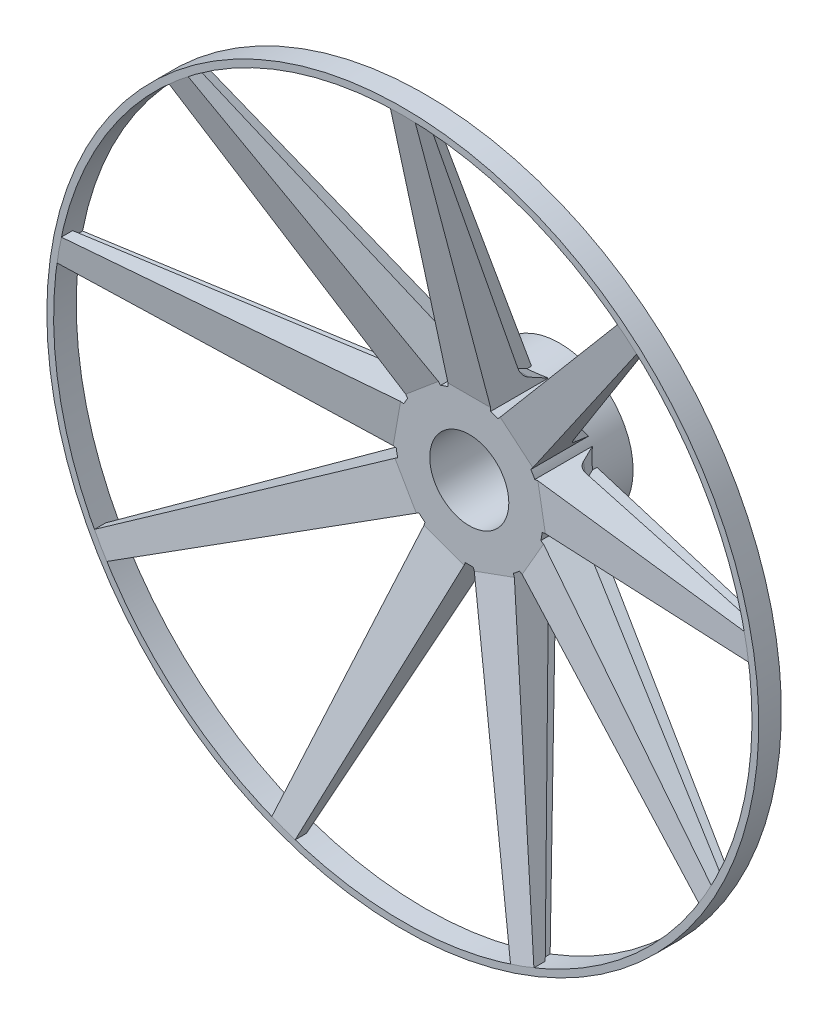
SolidWorks part; units mm, degrees
ref_plane "Front Plane" through (0, 0, 0) normal (0, 0, 1) x (1, 0, 0)
ref_plane "Top Plane" through (0, 0, 0) normal (0, 1, 0) x (1, 0, 0)
ref_plane "Right Plane" through (0, 0, 0) normal (1, 0, 0) x (0, 0, -1)
sketch "Sketch1" plane through (0, 0, 0) normal (0, 0, 1) x (1, 0, 0)
  line L0 (-20.031, 0) -> (20.031, 0) construction
  line L1 (0, 20.031) -> (0, -20.031) construction
  circle A1 centre (0, 0) radius 17.5
  circle A2 centre (0, 0) radius 32.5
  dimension "D1" = 35
  dimension "D2" = 65
extrude "Boss-Extrude1" add sketch "Sketch1" along normal blind 40
sketch "Sketch2" plane through (0, 0, 0) normal (0, 0, -1) x (-1, 0, 0)
  point P0 (0, 0)
sketch "Sketch3" plane through (0, 0, 0) normal (0, 1, 0) x (1, 0, 0)
  line L0 (0, 8.7146) -> (0, -51.2596) construction
sketch "Sketch4" plane through (0, 0, 0) normal (1, 0, 0) x (0, 0, -1)
  line L0 (-40, 32.5) -> (-15, 32.5)
  line L3 (-69.4044, 154.5) -> (-40, 32.5)
  line L4 (8.7146, 0) -> (-51.2596, 0) construction
  line L6 (-59.4044, 154.5) -> (-69.4044, 154.5)
  line L7 (-15, 32.5) -> (-59.4044, 154.5)
  dimension "D1" = 154.5
  dimension "D2" = 70
sketch "Sketch5" plane through (0, 0, 0) normal (0, 0, -1) x (-1, 0, 0)
extrude "Boss-Extrude2" add sketch "Sketch4" along normal blind 9.5 and the other way blind 9.5
sketch "Sketch6" plane through (0, 0, 40) normal (0, 0, 1) x (1, 0, 0)
  line L0 (-9.5, 32.5) -> (-9.5, 30.5512)
  line L1 (-9.5, 30.5512) -> (9.5, 30.5512)
  line L2 (9.5, 30.5512) -> (9.5, 32.5)
  line L3 (-9.5, 32.5) -> (9.5, 32.5)
  circle A0 centre (0, 0) radius 32.5
  circle M1 centre (0, 0) radius 32.5
extrude "Boss-Extrude3" add sketch "Sketch6" against normal blind 25 contours L3 L0 M1 | L3 L2 M1 | L1 L2 L0 M1 region at (-7.1355, 32.0758, 40) region at (0, 31.3512, 40) region at (7.1355, 32.0758, 40)
sketch "Sketch7" plane through (9.5, 0, 0) normal (1, 0, 0) x (0, 0, -1)
  line L0 (-15, 32.5) -> (-15.675, 34.3545)
  line L1 (-15, 32.5) -> (-59.4044, 154.5) construction
  line L2 (-15.675, 34.3545) -> (-14.4834, 31.0805)
  line L3 (-15, 31.0805) -> (-14.4834, 31.0805)
  line M2 (-15, 31.0805) -> (-15, 32.5)
extrude "Boss-Extrude4" add sketch "Sketch7" against normal blind 19 contours L3 L2 M2 region at (9.5, 31.5537, 14.8278)
sketch "Sketch10" plane through (-9.5, 0, 0) normal (-1, 0, 0) x (0, 0, 1)
  line L0 (64.4044, 154.5) -> (27.6856, 41.3109)
  line L1 (59.4044, 154.5) -> (69.4044, 154.5) construction
  line L3 (14.4834, 31.0805) -> (22.8914, 35.5794)
  line L4 (14.4834, 31.0805) -> (59.4044, 154.5)
  line L5 (59.4044, 154.5) -> (64.4044, 154.5)
  arc A0 (27.6856, 41.3109) -> (22.8914, 35.5794) centre (18.1735, 44.3966) cw
  point P5 (26.4427, 37.4796)
  point P6 (26.4427, 37.4796)
  dimension "D1" = 10
sketch "Sketch16" plane through (-9.5, 0, 0) normal (-1, 0, 0) x (0, 0, 1)
  line L5 (14.4834, 31.0805) -> (35.81, 31.0805) construction
  line L6 (40, 31.0805) -> (14.4834, 31.0805) construction
  line L7 (27.2417, 31.0805) -> (26.4088, 28.3283)
extrude "Cut-Extrude3" cut sketch "Sketch10" against normal blind 7
mirror "Mirror1" about plane through (0, 0, 0) normal (1, 0, 0) of "Cut-Extrude3"
sketch "Sketch18" plane through (0, -4.1926, 12.9241) normal (0, 0.3086, -0.9512) x (-1, 0, 0)
  line L0 (-2.5, 166.8339) -> (-5.5, 166.8339)
  line L2 (2.5, 166.8339) -> (5.5, 166.8339)
  line L3 (2.5, 166.8339) -> (9.5, 166.8339) construction
  line L4 (-2.5, 166.8339) -> (-9.5, 166.8339) construction
sketch3d "3DSketch1" plane through (0, 0, 0) normal (0, 0, 1) x (1, 0, 0)
sketch "Sketch20" plane through (0, 0, 0) normal (0, 0, -1) x (-1, 0, 0)
  line L0 (5.5, 154.5) -> (9.5, 29.7044)
  line L1 (9.5, 31.0805) -> (9.5, 28.3283) construction
  line L2 (9.5, 29.7044) -> (9.5, 154.5)
  line L3 (9.5, 154.5) -> (5.5, 154.5)
  line L4 (-5.5, 154.5) -> (-9.5, 31.0805)
  line L5 (-9.5, 31.0805) -> (-9.5, 154.5)
  line L6 (-9.5, 154.5) -> (-5.5, 154.5)
extrude "Cut-Extrude6" cut sketch "Sketch20" against normal through all
pattern_circular "CirPattern11" count 9 over 360 about axis through (0, 0, 0) along (0, 0, 1) of bodies 112
ref_plane "Plane1" through (0, 0, 69.4044) normal (0, 0, -1) x (-1, 0, 0)
sketch "Sketch21" plane through (0, 0, 69.4044) normal (0, 0, -1) x (-1, 0, 0)
  circle A0 centre (0, 0) radius 154.5
  circle A1 centre (0, 0) radius 157.5
extrude "Boss-Extrude5" add sketch "Sketch21" along normal blind 10
